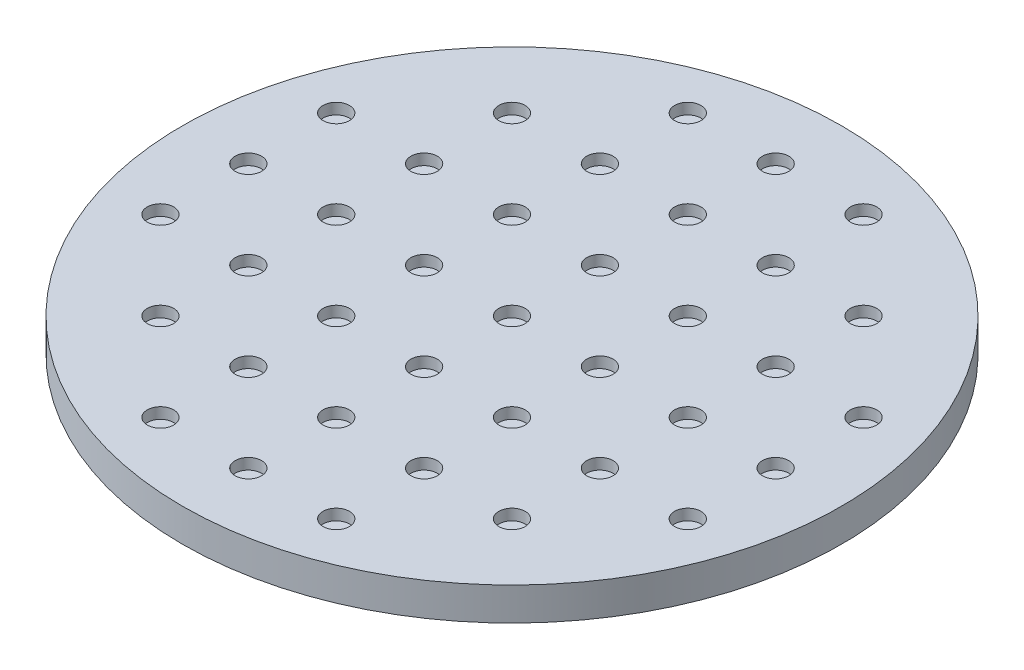
SolidWorks part; units mm, degrees
ref_plane "Front Plane" through (0, 0, 0) normal (0, 0, 1) x (1, 0, 0)
ref_plane "Top Plane" through (0, 0, 0) normal (0, 1, 0) x (1, 0, 0)
ref_plane "Right Plane" through (0, 0, 0) normal (1, 0, 0) x (0, 0, -1)
sketch "Sketch1" plane through (0, 0, 0) normal (0, 1, 0) x (1, 0, 0)
  circle A0 centre (0, 0) radius 381
  dimension "D1" = 762
extrude "Boss-Extrude1" add sketch "Sketch1" along normal mid plane 38.1
sketch "Sketch6" plane through (0, 19.05, 0) normal (0, 1, 0) x (1, 0, 0)
  line L0 (101.6, 101.6) -> (101.6, 203.2) construction
  line L1 (101.6, -101.6) -> (101.6, -203.2) construction
  line L2 (101.6, -101.6) -> (203.2, -101.6) construction
  line L3 (-101.6, 101.6) -> (-203.2, 101.6) construction
  circle A0 centre (0, 0) radius 15.25
  circle A1 centre (-101.6, 0) radius 15.25
  circle A2 centre (101.6, 0) radius 15.25
  circle A3 centre (-101.6, 101.6) radius 15.25
  circle A4 centre (0, 101.6) radius 15.25
  circle A5 centre (101.6, 101.6) radius 15.25
  circle A6 centre (-101.6, -101.6) radius 15.25
  circle A7 centre (0, -101.6) radius 15.25
  circle A8 centre (101.6, -101.6) radius 15.25
  circle A9 centre (101.6, 203.2) radius 15.25
  circle A10 centre (0, 203.2) radius 15.25
  circle A11 centre (-101.6, 203.2) radius 15.25
  circle A12 centre (101.6, 304.8) radius 15.25
  circle A13 centre (0, 304.8) radius 15.25
  circle A14 centre (-101.6, 304.8) radius 15.25
  circle A15 centre (101.6, -203.2) radius 15.25
  circle A16 centre (0, -203.2) radius 15.25
  circle A17 centre (-101.6, -203.2) radius 15.25
  circle A18 centre (101.6, -304.8) radius 15.25
  circle A19 centre (0, -304.8) radius 15.25
  circle A20 centre (-101.6, -304.8) radius 15.25
  circle A21 centre (203.2, -101.6) radius 15.25
  circle A22 centre (203.2, 0) radius 15.25
  circle A23 centre (203.2, 101.6) radius 15.25
  circle A24 centre (304.8, -101.6) radius 15.25
  circle A25 centre (304.8, 0) radius 15.25
  circle A26 centre (304.8, 101.6) radius 15.25
  circle A27 centre (-203.2, 101.6) radius 15.25
  circle A28 centre (-203.2, 0) radius 15.25
  circle A29 centre (-203.2, -101.6) radius 15.25
  circle A30 centre (-304.8, 101.6) radius 15.25
  circle A31 centre (-304.8, 0) radius 15.25
  circle A32 centre (-304.8, -101.6) radius 15.25
  circle A33 centre (-203.2, 203.2) radius 15.25
  circle A34 centre (203.2, 203.2) radius 15.25
  circle A35 centre (203.2, -203.2) radius 15.25
  circle A36 centre (-203.2, -203.2) radius 15.25
  dimension "D1" = 101.6
  dimension "D2" = 101.6
  dimension "D3" = 30.5
  dimension "D4" = 101.6
  dimension "D5" = 101.6
  dimension "D12" = 30.5
  dimension "D14" = 101.6
  dimension "D15" = 101.6
  dimension "D16" = 101.6
  dimension "D7" = 101.6
  dimension "D9" = 101.6
  dimension "D10" = 101.6
  dimension "D11" = 101.6
  dimension "D6" = 3
  dimension "D8" = 3
  dimension "D13" = 3
extrude "Cut-Extrude1" cut sketch "Sketch6" against normal blind 12.7
